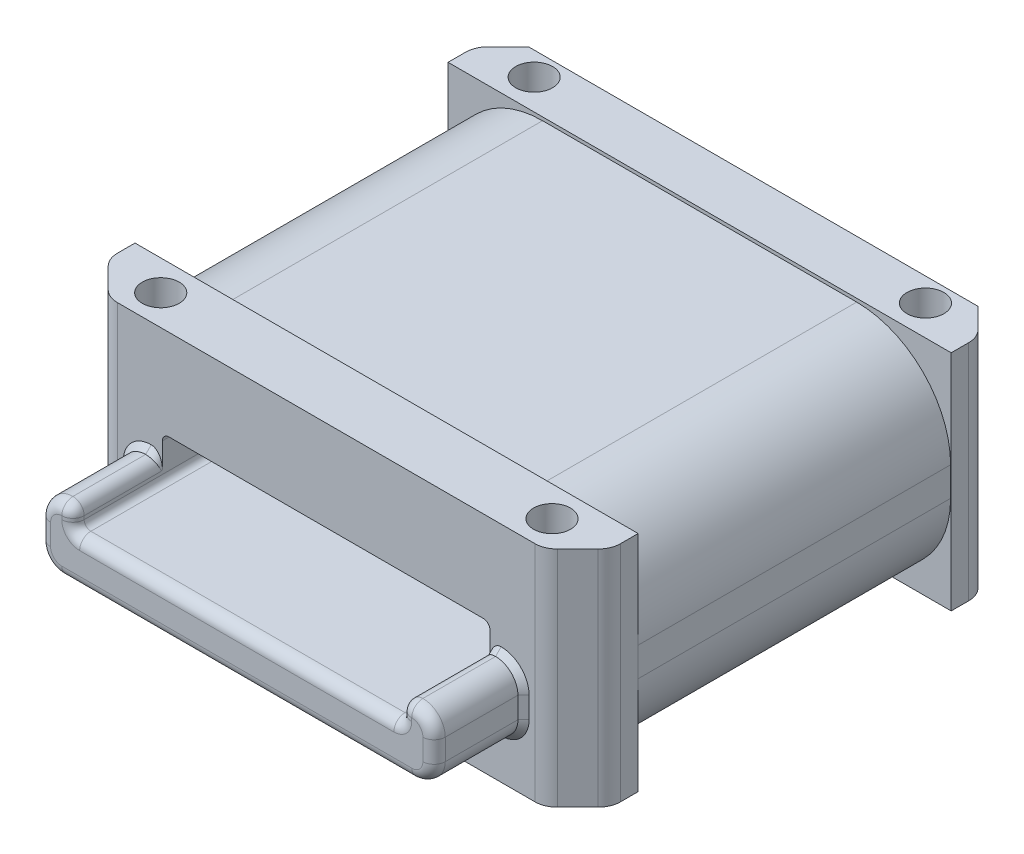
SolidWorks part; units mm, degrees
ref_plane "Front Plane" through (0, 0, 0) normal (0, 0, 1) x (1, 0, 0)
ref_plane "Top Plane" through (0, 0, 0) normal (0, 1, 0) x (1, 0, 0)
ref_plane "Right Plane" through (0, 0, 0) normal (1, 0, 0) x (0, 0, -1)
sketch "Sketch1" plane through (0, 0, 0) normal (0, 0, 1) x (1, 0, 0)
  line L1 (-14.65, 1.9) -> (14.65, 1.9)
  line L2 (-14.65, 1.9) -> (-14.65, -1.9)
  line L3 (-14.65, -1.9) -> (14.65, -1.9)
  line L4 (14.65, 1.9) -> (14.65, -1.9)
  line L13 (-17.05, -3.4) -> (17.05, -3.4)
  line L16 (-17.05, -3.4) -> (-17.05, 3.4)
  line L17 (-17.05, 3.4) -> (17.05, 3.4)
  line L18 (17.05, -3.4) -> (17.05, 3.4)
  line L19 (-17.05, -3.4) -> (17.05, 3.4) construction
  line L20 (-17.05, 3.4) -> (17.05, -3.4) construction
  point P0 (0, 0)
  point P6 (0, 0)
  point P10 (-14.65, 0)
  point P11 (0, 1.9)
  dimension "D1" = 29.3
  dimension "D2" = 3.8
  dimension "D3" = 1.5
  dimension "D4" = 2.4
extrude "Center Tube" add sketch "Sketch1" along normal mid plane 28
sketch "Sketch55" plane through (0, 0, 14) normal (0, 0, 1) x (1, 0, 0)
  line L0 (-17.05, 3.4) -> (17.05, 3.4)
  line L1 (-17.05, 0) -> (17.05, 0) construction
  line L4 (-17.05, -3.4) -> (17.05, -3.4)
  line L5 (17.05, 3.4) -> (-17.05, 3.4) construction
  line L6 (17.05, -3.4) -> (17.05, 3.4) construction
  line L7 (-17.05, 3.4) -> (-17.05, -3.4) construction
  arc A0 (-17.05, 3.4) -> (17.05, 3.4) centre (0, -76.8078) cw
  arc A1 (-17.05, -3.4) -> (17.05, -3.4) centre (0, 76.8078) ccw
  dimension "D1" = 82
extrude "Curvature" add sketch "Sketch55" against normal up to surface (28 mm away) up to face at (0, 0, -14)
sketch "Sketch2" plane through (0, 0, 14) normal (0, 0, 1) x (1, 0, 0)
  line L0 (-22.5, 10) -> (22.5, 10)
  line L13 (22.5, 10) -> (22.5, -10)
  line L14 (-22.5, -10) -> (22.5, -10)
  line L15 (-22.5, 10) -> (-22.5, -10)
  line L16 (-22.5, 10) -> (22.5, -10) construction
  line L17 (-22.5, -10) -> (22.5, 10) construction
  line L34 (14.65, -1.9) -> (14.65, 1.9) construction
  line L35 (-14.65, -1.9) -> (14.65, -1.9) construction
  line L36 (-14.65, 1.9) -> (-14.65, -1.9) construction
  line L37 (14.65, 1.9) -> (-14.65, 1.9) construction
  line L38 (14.65, -1.9) -> (14.65, 1.9)
  line L39 (-14.65, -1.9) -> (14.65, -1.9)
  line L40 (-14.65, 1.9) -> (-14.65, -1.9)
  line L41 (14.65, 1.9) -> (-14.65, 1.9)
  dimension "D2" = 20
  dimension "D3" = 45
extrude "Flange" add sketch "Sketch2" along normal blind 5.4
mirror "Mirror1" about plane through (0, 0, 0) normal (0, 0, 1) of "Flange"
hole_wizard "M3 Clearance Hole1" positions "Sketch9" profile "Sketch10" hole size "M2" standard "ANSI Metric" end condition through all
sketch "Sketch9" plane through (0, 10, 0) normal (0, 1, 0) x (1, 0, 0)
  line L2 (22.5, 19.4) -> (-22.5, 19.4) construction
  line L3 (-14.65, -19.4) -> (-14.65, 19.4) construction
  line L4 (22.5, 14) -> (-22.5, 14) construction
  line L5 (22.5, 19.4) -> (-22.5, 19.4) construction
  line L6 (-14.65, -19.4) -> (-14.65, 19.4) construction
  line L7 (22.5, 14) -> (-22.5, 14) construction
  line L8 (0, 14) -> (0, -17.2117) construction
  line L9 (-17.5, 19.4) -> (-17.5, 14) construction
  line L11 (0, 0) -> (27.5387, 0) construction
  point P17 (-17.5, 16.7)
  point P24 (-17.5, 16.7)
  point P31 (17.5, 16.7)
  point P33 (17.5, -16.7)
  point P34 (-17.5, -16.7)
  dimension "D1" = 35
sketch "Sketch10" plane through (-17.5, 10, 16.7) normal (1, 0, 0) x (0, 0, 1)
  line L0 (0, 0) -> (0, 20)
  line L1 (0, 20) -> (1.65, 20)
  line L2 (1.65, 20) -> (1.65, 0)
  line L5 (1.65, 0) -> (0, 0)
  line L11 (0, -6.35) -> (0, 107.95) construction
  dimension "Thru Hole Dia." = 3.3
  dimension "Thru Hole Depth" = 20
sketch "Sketch14" plane through (0, 0, 19.4) normal (0, 0, 1) x (1, 0, 0)
  line L0 (-14.65, 0) -> (-17.65, 0)
  line L1 (-14.65, 1.9) -> (-14.65, -1.9) construction
  line L2 (-17.65, 0) -> (-17.65, -5.9)
  line L3 (-17.65, -5.9) -> (17.65, -5.9)
  line L4 (17.65, -5.9) -> (17.65, 0)
  line L5 (17.65, 0) -> (14.65, 0)
  line L7 (-14.65, 0) -> (-14.65, -1.9)
  line L8 (-14.65, -1.9) -> (14.65, -1.9)
  line L9 (14.65, -1.9) -> (14.65, 0)
  line L11 (-14.65, -1.9) -> (14.65, -1.9) construction
  line L12 (14.65, -1.9) -> (14.65, 1.9) construction
  dimension "D1" = 3
  dimension "D2" = 3
  dimension "D3" = 4
extrude "Boss-Extrude3" add sketch "Sketch14" along normal blind 8
fillet "Fillet Center Edges" radius 2.5 4 edges at (-17.05, -3.4, 0) (17.05, 3.4, 0) (17.05, -3.4, 0) (-17.05, 3.4, 0)
chamfer "Chamfer1" distance 3 angle 45 4 edges at (-22.5, 0, -19.4) (22.5, 0, -19.4) (22.5, 0, 19.4) (-22.5, 0, 19.4)
fillet "Fillet4" radius 2 4 edges at (17.65, 0, 23.4) (-17.65, 0, 23.4) (17.65, -5.9, 23.4) (-17.65, -5.9, 23.4)
fillet "Fillet6" radius 0.6 4 edges at (-14.65, 1.9, 0) (14.65, 1.9, 0) (14.65, -1.9, 4) (-14.65, -1.9, 4)
chamfer "Chamfer2" distance 0.5 angle 45 25 edges at (-15.15, 0, 19.4) (15.15, 0, 19.4) (-17.0642, -0.5858, 19.4) (17.0642, -0.5858, 19.4) (-17.65, -2.95, 19.4) (17.65, -2.95, 19.4) (-17.0642, -5.3142, 19.4) (17.0642, -5.3142, 19.4) (0, -5.9, 19.4) (0, 5.1922, 14) (0, 5.1922, -14) (0, -5.1922, 14) (0, -5.1922, -14) (16.4727, -2.9472, 14) (-16.4727, -2.9472, 14) (17.05, 0, 14) (-17.05, 0, 14) (16.4727, 2.9472, 14) (-16.4727, 2.9472, 14) (16.4727, -2.9472, -14) (-16.4727, -2.9472, -14) (17.05, 0, -14) (-17.05, 0, -14) (16.4727, 2.9472, -14) (-16.4727, 2.9472, -14)
fillet "Fillet7" radius 2 6 edges at (22.5, 0, -16.4) (-22.5, 0, -16.4) (-19.5, 0, 19.4) (-22.5, 0, 16.4) (22.5, 0, 16.4) (19.5, 0, 19.4)
sketch "Sketch54" plane through (0, 0, 14) normal (0, 0, -1) x (-1, 0, 0)
  line L1 (14.05, -1.9) -> (-14.05, -1.9) construction
  line L2 (-14.65, -1.3) -> (-14.65, 1.3) construction
  line L4 (14.65, 1.3) -> (14.65, -1.3) construction
  line L5 (14.05, -1.9) -> (-14.05, -1.9) construction
  line L6 (-14.65, -1.3) -> (-14.65, 1.3) construction
  line L7 (-14.05, 1.9) -> (14.05, 1.9) construction
  line L8 (22.45, 1.3) -> (22.45, -1.3)
  line L9 (14.05, -9.7) -> (-14.05, -9.7)
  line L10 (-22.45, -1.3) -> (-22.45, 1.3)
  line L11 (-14.05, 9.7) -> (14.05, 9.7)
  line L12 (15.15, 1.3) -> (15.15, -1.3)
  line L13 (14.05, -2.4) -> (-14.05, -2.4)
  line L14 (-15.15, -1.3) -> (-15.15, 1.3)
  line L15 (-14.05, 2.4) -> (14.05, 2.4)
  arc A0 (14.65, 1.3) -> (14.05, 1.9) centre (14.05, 1.3) ccw construction
  arc A1 (14.05, -1.9) -> (14.65, -1.3) centre (14.05, -1.3) ccw construction
  arc A2 (-14.65, -1.3) -> (-14.05, -1.9) centre (-14.05, -1.3) ccw construction
  arc A3 (-14.05, 1.9) -> (-14.65, 1.3) centre (-14.05, 1.3) ccw construction
  arc A4 (14.65, 1.3) -> (14.05, 1.9) centre (14.05, 1.3) ccw construction
  arc A5 (14.05, -1.9) -> (14.65, -1.3) centre (14.05, -1.3) ccw construction
  arc A6 (-14.65, -1.3) -> (-14.05, -1.9) centre (-14.05, -1.3) ccw construction
  arc A7 (-14.05, 1.9) -> (-14.65, 1.3) centre (-14.05, 1.3) ccw construction
  arc A8 (14.05, -9.7) -> (22.45, -1.3) centre (14.05, -1.3) ccw
  arc A9 (-22.45, -1.3) -> (-14.05, -9.7) centre (-14.05, -1.3) ccw
  arc A10 (-14.05, 9.7) -> (-22.45, 1.3) centre (-14.05, 1.3) ccw
  arc A11 (22.45, 1.3) -> (14.05, 9.7) centre (14.05, 1.3) ccw
  arc A12 (14.05, -2.4) -> (15.15, -1.3) centre (14.05, -1.3) ccw
  arc A13 (-15.15, -1.3) -> (-14.05, -2.4) centre (-14.05, -1.3) ccw
  arc A14 (-14.05, 2.4) -> (-15.15, 1.3) centre (-14.05, 1.3) ccw
  arc A15 (15.15, 1.3) -> (14.05, 2.4) centre (14.05, 1.3) ccw
  dimension "D1" = 7.8
  dimension "D2" = 0.5
extrude "Boss-Extrude4" add sketch "Sketch54" along normal up to surface (28 mm away) separate body up to face at (0, 0, -14)
chamfer "Chamfer3" distance 0.6 angle 45 10 edges at (0, 1.9, -19.4) (-14.4743, 1.7243, -19.4) (14.4743, 1.7243, -19.4) (-14.65, 0, -19.4) (14.65, 0, -19.4) (-14.4743, -1.7243, -19.4) (14.4743, -1.7243, -19.4) (0, -1.9, -19.4) (0, -10, -19.4) (0, 10, -19.4)
fillet "Fillet8" radius 1 20 edges at (-19.5, 0, -19.4) (19.5, 0, -19.4) (-17.0642, -5.3142, 27.4) (-17.65, -2.95, 27.4) (-17.0642, -0.5858, 27.4) (-15.15, 0, 27.4) (-14.65, -0.65, 27.4) (-14.4743, -1.7243, 27.4) (0, -1.9, 27.4) (14.4743, -1.7243, 27.4) (14.65, -0.65, 27.4) (15.15, 0, 27.4) (17.0642, -0.5858, 27.4) (17.65, -2.95, 27.4) (17.0642, -5.3142, 27.4) (0, -5.9, 27.4) (14.65, 0, 23.65) (-14.65, 0, 23.65) (14.65, 0.25, 19.65) (-14.65, 0.25, 19.65)
